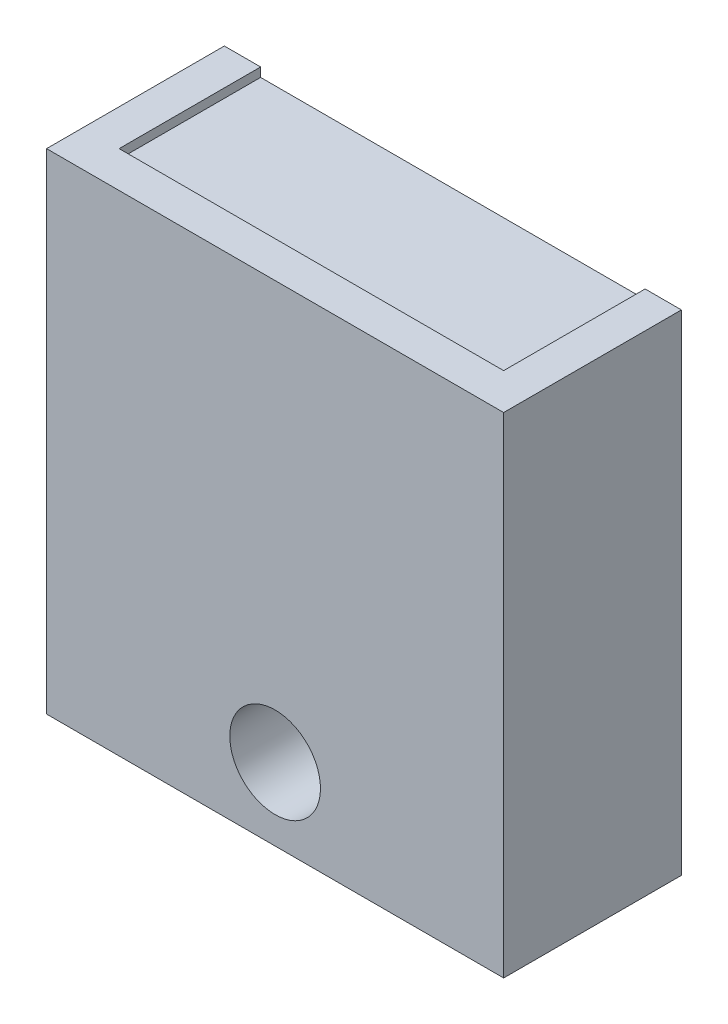
SolidWorks part; units mm, degrees
ref_plane "Plan de face" through (0, 0, 0) normal (0, 0, 1) x (1, 0, 0)
ref_plane "Plan de dessus" through (0, 0, 0) normal (0, 1, 0) x (1, 0, 0)
ref_plane "Plan de droite" through (0, 0, 0) normal (1, 0, 0) x (0, 0, -1)
sketch "Sketch2" plane through (0, 0, 0) normal (0, 0, 1) x (1, 0, 0)
  line L1 (0, 0) -> (-25.2, 0)
  line L2 (0, 0) -> (0, 27)
  line L3 (0, 27) -> (-25.2, 27)
  line L4 (-25.2, 0) -> (-25.2, 27)
  dimension "D1" = 25.2
  dimension "D2" = 27
extrude "Boss-Extrude2" add sketch "Sketch2" along normal blind 2
sketch "Sketch3" plane through (0, 0, 0) normal (0, 0, -1) x (-1, 0, 0)
  line L0 (25.2, 0) -> (0, 0) construction
  line L1 (0, 27) -> (2, 27)
  line L2 (0, 27) -> (0, 0)
  line L3 (0, 0) -> (2, 0)
  line L4 (2, 27) -> (2, 0)
  line L5 (0, 27) -> (25.2, 27) construction
  line L6 (25.2, 0) -> (23.2, 0)
  line L7 (25.2, 0) -> (25.2, 27)
  line L8 (25.2, 27) -> (23.2, 27)
  line L9 (23.2, 0) -> (23.2, 27)
  line L11 (2, 27) -> (23.2, 27)
  line L12 (2, 27) -> (2, 25)
  line L13 (2, 25) -> (23.2, 25)
  line L14 (23.2, 27) -> (23.2, 25)
  line M3 (0, 27) -> (0, 0)
  line M4 (0, 0) -> (25.2, 0)
  line M5 (25.2, 0) -> (25.2, 27)
  line M6 (25.2, 27) -> (0, 27)
  dimension "D1" = 2
  dimension "D2" = 2
  dimension "D3" = 2
extrude "Boss-Extrude3" add sketch "Sketch3" along normal blind 7.8 contours L4 M6 M3 M4 | L4 L13 L9 M6 | L9 M4 M5 M6 region at (-1, 13.5, 0) region at (-12.6, 26, 0) region at (-24.2, 13.5, 0)
sketch "Sketch8" plane through (0, 0, 0) normal (0, 0, -1) x (-1, 0, 0)
  line L0 (23.2, 0) -> (23.2, 25) construction
  line L1 (2, 0) -> (23.2, 0)
  line L2 (2, 0) -> (2, 8.1631)
  line L3 (2, 8.1631) -> (23.2, 8.1631)
  line L4 (23.2, 0) -> (23.2, 8.1631)
  line L5 (23.2, 8.1631) -> (2, 8.1631) construction
  line L7 (4.35, 8.1631) -> (2, 8.1631)
  line L8 (4.35, 8.1631) -> (4.35, 0)
  line L9 (4.35, 0) -> (2, 0)
  line L10 (2, 8.1631) -> (2, 0)
  line L11 (9.35, 8.1631) -> (15.8479, 8.1631)
  line L12 (9.35, 8.1631) -> (9.35, 0)
  line L13 (9.35, 0) -> (15.8479, 0)
  line L14 (15.8479, 8.1631) -> (15.8479, 0)
  line L15 (20.85, 8.1631) -> (23.2, 8.1631)
  line L16 (20.85, 8.1631) -> (20.85, 0)
  line L17 (20.85, 0) -> (23.2, 0)
  line L18 (23.2, 8.1631) -> (23.2, 0)
  line M10 (2, 25) -> (2, 0)
  line M11 (2, 0) -> (23.2, 0)
  line M12 (23.2, 0) -> (23.2, 25)
  dimension "D1" = 6.4979
extrude "Boss-Extrude6" add sketch "Sketch8" along normal blind 7.8 contours L8 L3 M10 M11 | L14 L3 L12 M11 | L3 L16 M11 M12 region at (-3.175, 4.0815, 0) region at (-12.5989, 4.0815, 0) region at (-22.025, 4.0815, 0)
sketch "Sketch9" plane through (0, 0, 0) normal (0, 0, -1) x (-1, 0, 0)
  line L1 (4.35, 8.1631) -> (9.35, 8.1631)
  line L2 (4.35, 8.1631) -> (4.35, 0)
  line L3 (4.35, 0) -> (9.35, 0)
  line L4 (9.35, 8.1631) -> (9.35, 0)
  line L5 (15.8479, 8.1631) -> (20.85, 8.1631)
  line L6 (15.8479, 8.1631) -> (15.8479, 0)
  line L7 (15.8479, 0) -> (20.85, 0)
  line L8 (20.85, 8.1631) -> (20.85, 0)
extrude "Boss-Extrude7" add sketch "Sketch9" along normal blind 1.3
sketch "Sketch10" plane through (0, 27, 0) normal (0, 1, 0) x (1, 0, 0)
  line L0 (0, -2) -> (-25.2, -2) construction
  line L1 (-2, 7.8) -> (-23.2, 7.8)
  line L2 (-2, 7.8) -> (-2, 0)
  line L3 (-2, 0) -> (-23.2, 0)
  line L4 (-23.2, 7.8) -> (-23.2, 0)
  line L5 (-25.2, -2) -> (-25.2, 7.8) construction
  dimension "D1" = 2
  dimension "D2" = 2
extrude "Cut-Extrude3" cut sketch "Sketch10" against normal blind 0.5
sketch "Sketch12" plane through (0, 0, 2) normal (0, 0, 1) x (1, 0, 0)
  line L1 (0, 0) -> (0, 27) construction
  line L2 (-25.2, 0) -> (0, 0) construction
  circle A0 centre (-12.6, 4) radius 1
  dimension "D1" = 2
  dimension "D2" = 12.6
  dimension "D3" = 4
extrude "Cut-Extrude4" cut sketch "Sketch12" against normal through all
sketch "Sketch13" plane through (0, 0, 2) normal (0, 0, 1) x (1, 0, 0)
  circle A0 centre (-12.6, 4) radius 2.5
  dimension "D1" = 5
extrude "Cut-Extrude5" cut sketch "Sketch13" against normal blind 5.6348
sketch "Sketch14" plane through (0, 25, 0) normal (0, -1, 0) x (1, 0, 0)
  line L1 (-2, 0) -> (-23.2, 0)
  line L2 (-2, 0) -> (-2, -7.8)
  line L3 (-2, -7.8) -> (-23.2, -7.8)
  line L4 (-23.2, 0) -> (-23.2, -7.8)
extrude "Boss-Extrude8" add sketch "Sketch14" along normal blind 1
sketch "Sketch15" plane through (0, 0, 0) normal (0, 0, -1) x (-1, 0, 0)
  line L1 (2, 24) -> (23.2, 24)
  line L2 (2, 24) -> (2, 8.1631)
  line L3 (2, 8.1631) -> (23.2, 8.1631)
  line L4 (23.2, 24) -> (23.2, 8.1631)
extrude "Boss-Extrude9" add sketch "Sketch15" along normal blind 1.05
sketch "Sketch16" plane through (-20.85, 0, 0) normal (1, 0, 0) x (0, 0, -1)
  line L1 (1.3, 8.1631) -> (7.8, 8.1631)
  line L2 (1.3, 8.1631) -> (1.3, 0)
  line L3 (1.3, 0) -> (7.8, 0)
  line L4 (7.8, 8.1631) -> (7.8, 0)
extrude "Boss-Extrude10" add sketch "Sketch16" along normal blind 0.25
sketch "Sketch17" plane through (-4.35, 0, 0) normal (-1, 0, 0) x (0, 0, 1)
  line L1 (-1.3, 8.1631) -> (-7.8, 8.1631)
  line L2 (-1.3, 8.1631) -> (-1.3, 0)
  line L3 (-1.3, 0) -> (-7.8, 0)
  line L4 (-7.8, 8.1631) -> (-7.8, 0)
extrude "Boss-Extrude11" add sketch "Sketch17" along normal blind 0.25
sketch "Sketch18" plane through (-15.8479, 0, 0) normal (-1, 0, 0) x (0, 0, 1)
  line L1 (-1.3, 8.1631) -> (-7.8, 8.1631)
  line L2 (-1.3, 8.1631) -> (-1.3, 0)
  line L3 (-1.3, 0) -> (-7.8, 0)
  line L4 (-7.8, 8.1631) -> (-7.8, 0)
extrude "Boss-Extrude12" add sketch "Sketch18" along normal blind 0.15
sketch "Sketch19" plane through (-9.35, 0, 0) normal (1, 0, 0) x (0, 0, -1)
  line L1 (1.3, 8.1631) -> (7.8, 8.1631)
  line L2 (1.3, 8.1631) -> (1.3, 0)
  line L3 (1.3, 0) -> (7.8, 0)
  line L4 (7.8, 8.1631) -> (7.8, 0)
extrude "Boss-Extrude13" add sketch "Sketch19" along normal blind 0.15
sketch "Sketch20" plane through (-23.2, 0, 0) normal (1, 0, 0) x (0, 0, -1)
  line L1 (1.05, 24) -> (7.8, 24)
  line L2 (1.05, 24) -> (1.05, 8.1631)
  line L3 (1.05, 8.1631) -> (7.8, 8.1631)
  line L4 (7.8, 24) -> (7.8, 8.1631)
extrude "Boss-Extrude14" add sketch "Sketch20" along normal blind 1
sketch "Sketch21" plane through (-2, 0, 0) normal (-1, 0, 0) x (0, 0, 1)
  line L1 (-1.05, 24) -> (-7.8, 24)
  line L2 (-1.05, 24) -> (-1.05, 8.1631)
  line L3 (-1.05, 8.1631) -> (-7.8, 8.1631)
  line L4 (-7.8, 24) -> (-7.8, 8.1631)
extrude "Boss-Extrude15" add sketch "Sketch21" along normal blind 1
sketch "Sketch22" plane through (0, 24, 0) normal (0, -1, 0) x (1, 0, 0)
  line L1 (-3, -7.8) -> (-22.2, -7.8)
  line L2 (-3, -7.8) -> (-3, -1.05)
  line L3 (-3, -1.05) -> (-22.2, -1.05)
  line L4 (-22.2, -7.8) -> (-22.2, -1.05)
extrude "Boss-Extrude16" add sketch "Sketch22" along normal blind 12
